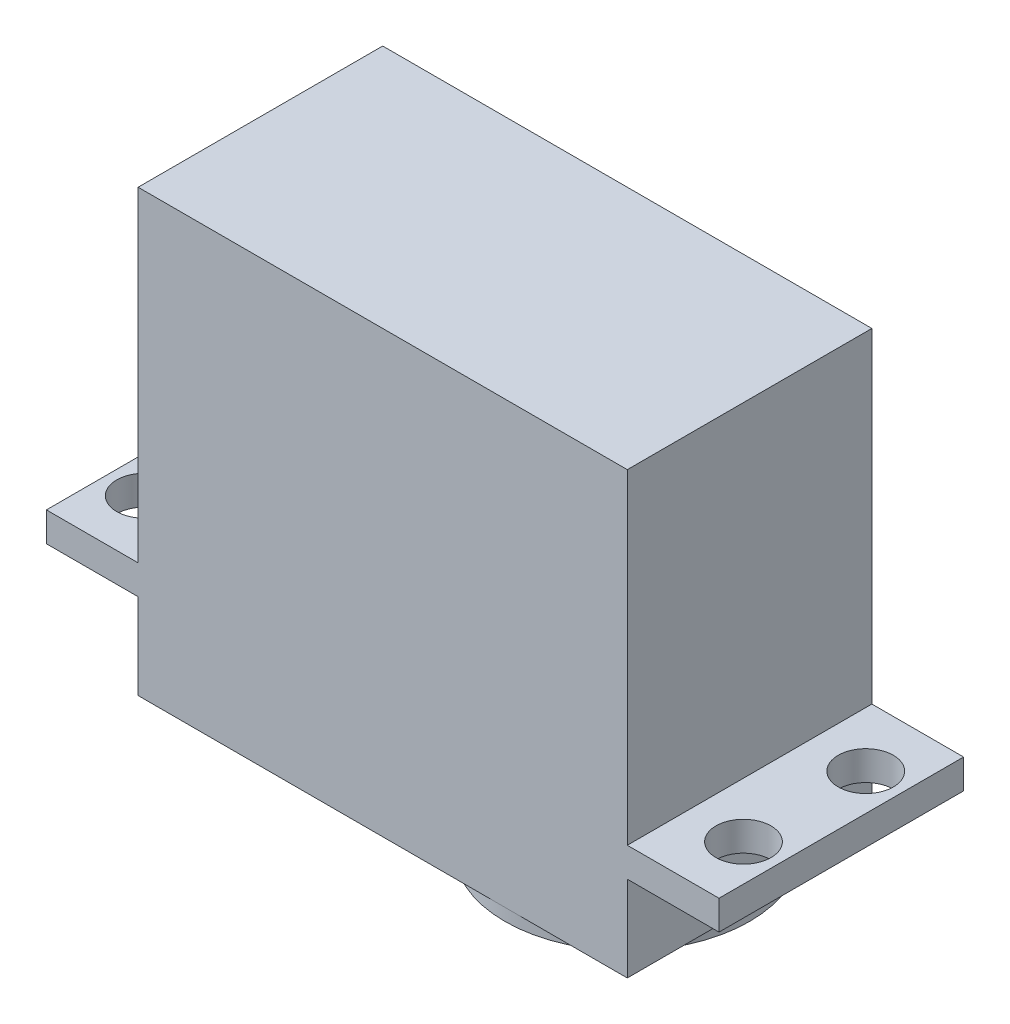
SolidWorks part; units mm, degrees
ref_plane "Front Plane" through (0, 0, 0) normal (0, 0, 1) x (1, 0, 0)
ref_plane "Top Plane" through (0, 0, 0) normal (0, 1, 0) x (1, 0, 0)
ref_plane "Right Plane" through (0, 0, 0) normal (1, 0, 0) x (0, 0, -1)
sketch "Sketch1" plane through (0, 0, 0) normal (0, 1, 0) x (1, 0, 0)
  line L1 (-20, -10) -> (20, -10)
  line L2 (-20, -10) -> (-20, 10)
  line L3 (-20, 10) -> (20, 10)
  line L4 (20, -10) -> (20, 10)
  line L5 (-20, -10) -> (20, 10) construction
  line L6 (-20, 10) -> (20, -10) construction
  point P0 (0, 0)
  dimension "D1" = 40
  dimension "D2" = 20
extrude "Boss-Extrude1" add sketch "Sketch1" along normal blind 36
ref_plane "Plane1" through (0, 7, 0) normal (0, 1, 0) x (1, 0, 0)
sketch "Sketch2" plane through (0, 7, 0) normal (0, 1, 0) x (1, 0, 0)
  line L0 (20, 10) -> (-20, 10) construction
  line L1 (-27.5, -10) -> (27.5, -10)
  line L2 (-27.5, -10) -> (-27.5, 10)
  line L3 (-27.5, 10) -> (27.5, 10)
  line L4 (27.5, -10) -> (27.5, 10)
  line L5 (-27.5, -10) -> (27.5, 10) construction
  line L6 (-27.5, 10) -> (27.5, -10) construction
  point P0 (0, 0)
  dimension "D1" = 55
extrude "Boss-Extrude2" add sketch "Sketch2" along normal blind 2.4
hole_wizard "M4 Clearance Hole1" positions "Sketch4" profile "Sketch3" hole size "M4" standard "ISO" end condition through all
sketch "Sketch4" plane through (0, 7, 0) normal (0, -1, 0) x (-1, 0, 0)
  line L0 (-24.5, 5) -> (-24.5, -5) construction
  line L1 (-24.5, -5) -> (-24.5, 0) construction
  line L2 (-24.5, 0) -> (0, 0) construction
  point P0 (-24.5, 5)
  point P2 (-24.5, -5)
  dimension "D1" = 24.5
  dimension "D2" = 10
sketch "Sketch3" plane through (24.5, 7, -5) normal (1, 0, 0) x (0, 0, -1)
  line L0 (0, 0) -> (0, 29)
  line L1 (0, 29) -> (2.25, 29)
  line L2 (2.25, 29) -> (2.25, 0)
  line L5 (2.25, 0) -> (0, 0)
  line L11 (0, -6.35) -> (0, 107.95) construction
  dimension "Thru Hole Dia." = 4.5
  dimension "Thru Hole Depth" = 29
mirror "Mirror1" about plane through (0, 0, 0) normal (1, 0, 0) of "M4 Clearance Hole1"
sketch "Sketch5" plane through (0, 0, 0) normal (0, -1, 0) x (1, 0, 0)
  line L0 (20, 10) -> (20, -10) construction
  circle A0 centre (10, 0) radius 10
  dimension "D1" = 10
  dimension "D2" = 20
extrude "Boss-Extrude3" add sketch "Sketch5" along normal blind 1
